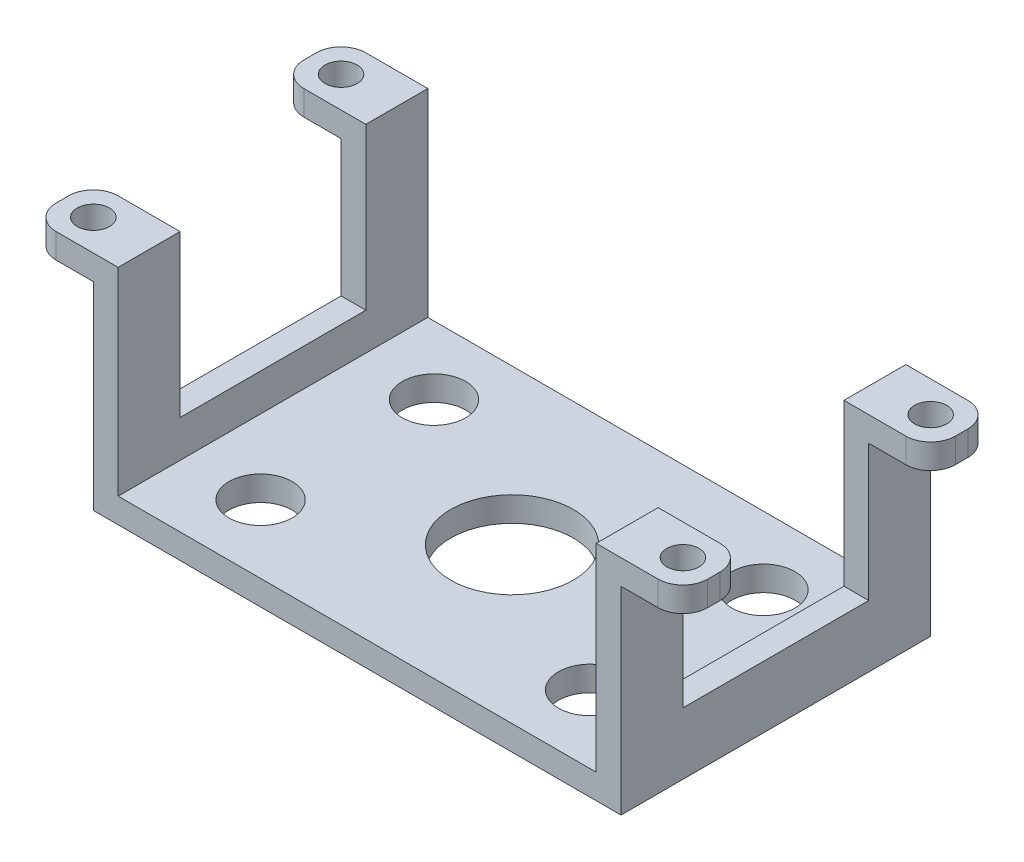
SolidWorks part; units mm, degrees
ref_plane "Płaszczyzna przednia" through (0, 0, 0) normal (0, 0, 1) x (1, 0, 0)
ref_plane "Płaszczyzna górna" through (0, 0, 0) normal (0, 1, 0) x (1, 0, 0)
ref_plane "Płaszczyzna prawa" through (0, 0, 0) normal (1, 0, 0) x (0, 0, -1)
sketch "Szkic1" plane through (0, 0, 0) normal (0, 1, 0) x (1, 0, 0)
  line L1 (21.3, -12.5) -> (-21.3, -12.5)
  line L2 (21.3, -12.5) -> (21.3, 12.5)
  line L3 (21.3, 12.5) -> (-21.3, 12.5)
  line L4 (-21.3, -12.5) -> (-21.3, 12.5)
  line L5 (21.3, -12.5) -> (-21.3, 12.5) construction
  line L6 (21.3, 12.5) -> (-21.3, -12.5) construction
  point P0 (0, 0)
  dimension "D1" = 25
  dimension "D2" = 42.6
extrude "Dodanie-wyciągnięcie2" add sketch "Szkic1" along normal blind 18
shell "Skorupa5" thickness 2 removed face at (0, 9, -12.5) removed face at (0, 9, 12.5) removed face at (0, 18, 0)
sketch "Szkic2" plane through (0, 18, 0) normal (0, 1, 0) x (1, 0, 0)
  line L0 (-21.3, 12.5) -> (-21.3, -12.5) construction
  line L1 (-21.3, 12.5) -> (-24.3, 12.5)
  line L2 (-21.3, 12.5) -> (-21.3, 7.5)
  line L3 (-21.3, 7.5) -> (-24.3, 7.5)
  line L4 (-26.3, 10.5) -> (-26.3, 9.5)
  line L5 (-26.3, 12.5) -> (-21.3, 7.5) construction
  line L6 (-26.3, 7.5) -> (-21.3, 12.5) construction
  line L7 (0, 12.5) -> (0, -12.5) construction
  line L8 (19.3, 12.5) -> (-19.3, 12.5) construction
  line L9 (-19.3, -12.5) -> (19.3, -12.5) construction
  line L10 (-19.3, 0) -> (19.3, 0) construction
  line L11 (-19.3, 12.5) -> (-19.3, -12.5) construction
  line L12 (19.3, -12.5) -> (19.3, 12.5) construction
  line L13 (-21.3, -7.5) -> (-24.3, -7.5)
  line L14 (-26.3, -10.5) -> (-26.3, -9.5)
  line L15 (-21.3, -12.5) -> (-24.3, -12.5)
  line L16 (-21.3, -12.5) -> (-21.3, -7.5)
  line L17 (21.3, -12.5) -> (21.3, -7.5)
  line L18 (21.3, -12.5) -> (24.3, -12.5)
  line L19 (26.3, -10.5) -> (26.3, -9.5)
  line L20 (21.3, -7.5) -> (24.3, -7.5)
  line L21 (21.3, 7.5) -> (24.3, 7.5)
  line L22 (26.3, 10.5) -> (26.3, 9.5)
  line L23 (21.3, 12.5) -> (24.3, 12.5)
  line L24 (21.3, 12.5) -> (21.3, 7.5)
  circle A0 centre (-23.8, 10) radius 1.3
  arc A1 (-24.3, 7.5) -> (-26.3, 9.5) centre (-24.3, 9.5) cw
  arc A2 (-24.3, 12.5) -> (-26.3, 10.5) centre (-24.3, 10.5) ccw
  arc A3 (-24.3, -7.5) -> (-26.3, -9.5) centre (-24.3, -9.5) ccw
  arc A4 (-24.3, -12.5) -> (-26.3, -10.5) centre (-24.3, -10.5) cw
  circle A5 centre (-23.8, -10) radius 1.3
  circle A6 centre (23.8, -10) radius 1.3
  arc A7 (24.3, -12.5) -> (26.3, -10.5) centre (24.3, -10.5) ccw
  arc A8 (24.3, -7.5) -> (26.3, -9.5) centre (24.3, -9.5) cw
  arc A9 (24.3, 7.5) -> (26.3, 9.5) centre (24.3, 9.5) ccw
  arc A10 (24.3, 12.5) -> (26.3, 10.5) centre (24.3, 10.5) cw
  circle A11 centre (23.8, 10) radius 1.3
  dimension "D3" = 2
  dimension "D1" = 5
  dimension "D2" = 5
  dimension "D4" = 7.5
extrude "Dodanie-wyciągnięcie3" add sketch "Szkic2" against normal blind 2
sketch "Szkic3" plane through (0, 2, 0) normal (0, 1, 0) x (1, 0, 0)
  line L1 (19.3, -12.5) -> (19.3, 12.5) construction
  line L2 (0, 12.5) -> (0, -12.5) construction
  line L3 (19.3, 12.5) -> (-19.3, 12.5) construction
  line L4 (-19.3, -12.5) -> (19.3, -12.5) construction
  circle A0 centre (0, 0) radius 4.95
  circle A2 centre (13.3, 7) radius 2.55
  circle A3 centre (-13.3, -7) radius 2.55
  circle A4 centre (13.3, -7) radius 2.55
  circle A5 centre (-13.3, 7) radius 2.55
  point P9 (13.3, 0)
  point P14 (0, 0)
  dimension "D1" = 6
  dimension "D3" = 9.9
  dimension "D4" = 5.1
  dimension "D5" = 7
  dimension "D2" = 5.5
  dimension "D6" = 2
extrude "Wytnij-wyciągnięcie1" cut sketch "Szkic3" against normal blind 2
sketch "Szkic4" plane through (-21.3, 0, 0) normal (-1, 0, 0) x (0, 0, 1)
  line L0 (-7.5, 18) -> (7.5, 18) construction
  line L1 (7.5, 5) -> (-7.5, 5)
  line L2 (7.5, 5) -> (7.5, 18)
  line L3 (7.5, 18) -> (-7.5, 18)
  line L4 (-7.5, 5) -> (-7.5, 18)
  line L5 (7.5, 5) -> (-7.5, 18) construction
  line L6 (7.5, 18) -> (-7.5, 5) construction
  point P0 (0, 11.5)
  dimension "D1" = 15
  dimension "D2" = 13
extrude "Wytnij-wyciągnięcie2" cut sketch "Szkic4" against normal through all both and the other way through all
